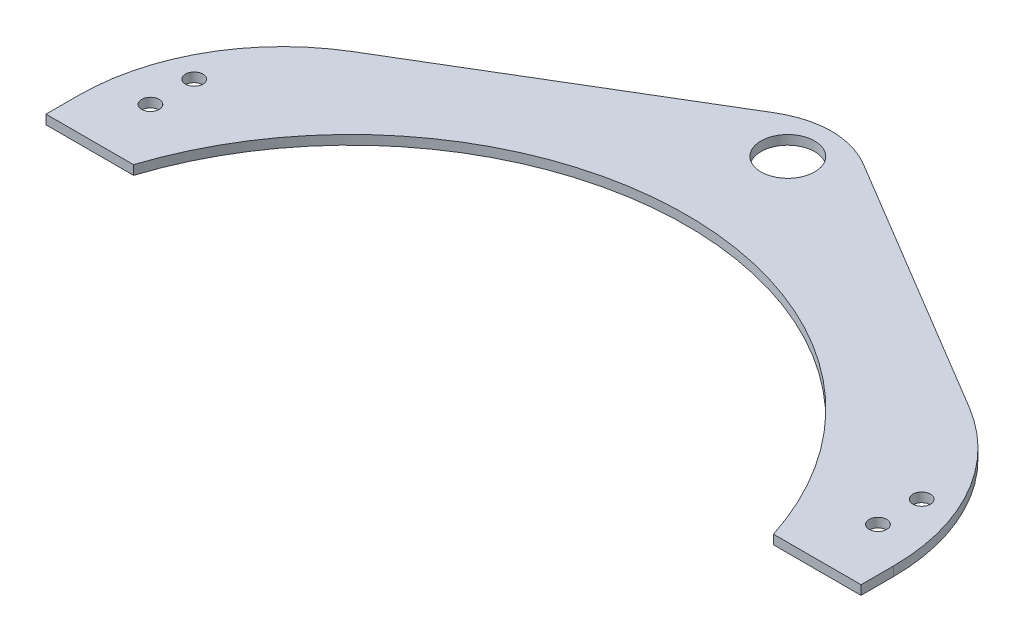
SolidWorks part; units mm, degrees
ref_plane "Front Plane" through (0, 0, 0) normal (0, 0, 1) x (1, 0, 0)
ref_plane "Top Plane" through (0, 0, 0) normal (0, 1, 0) x (1, 0, 0)
ref_plane "Right Plane" through (0, 0, 0) normal (1, 0, 0) x (0, 0, -1)
sketch "Sketch1" plane through (0, 0, 0) normal (0, 1, 0) x (1, 0, 0)
  line L1 (54.85, 0) -> (54.85, 39.9)
  line L2 (109.7, 0) -> (124.7, 0)
  line L3 (0, 0) -> (-15, 0)
  line L4 (124.7, 0) -> (124.7, 16.895)
  line L5 (-15, 0) -> (-15, 16.895)
  line L6 (54.85, 0) -> (54.85, 57.3)
  line L7 (54.85, 57.3) -> (54.85, 64.8)
  line L8 (54.85, 64.8) -> (54.7052, 64.8)
  line L9 (54.85, 64.8) -> (54.9948, 64.8)
  line L10 (62.4068, 62.6719) -> (117.4016, 29.7668)
  line L11 (47.2932, 62.6719) -> (-7.7016, 29.7668)
  line L12 (117.2, 0) -> (117.2, 10.4)
  line L13 (117.2, 10.4) -> (117.2, 17.9)
  line L14 (-7.5, 0) -> (-7.5, 10.4)
  line L15 (107.6704, 35.5893) -> (62.4068, 62.6719)
  line L16 (124.7, 5.5549) -> (124.7, 0)
  line L17 (47.2932, 62.6719) -> (2.0296, 35.5893)
  line L18 (-15, 5.5549) -> (-15, 0)
  line L19 (-7.5, 10.4) -> (-7.5, 17.9)
  circle A1 centre (54.85, 57.3) radius 4.6
  arc A2 (54.7052, 64.8) -> (62.4068, 62.6719) centre (54.7052, 49.8) cw
  arc A3 (54.9948, 64.8) -> (47.2932, 62.6719) centre (54.9948, 49.8) ccw
  arc A4 (-15, 16.895) -> (-7.7016, 29.7668) centre (0, 16.895) cw
  arc A5 (124.7, 16.895) -> (117.4016, 29.7668) centre (109.7, 16.895) ccw
  circle A6 centre (117.2, 17.9) radius 1.5
  circle A7 centre (117.2, 10.4) radius 1.5
  arc A10 (107.6704, 35.5893) -> (124.7, 5.5549) centre (89.7, 5.5549) cw
  arc A11 (2.0296, 35.5893) -> (-15, 5.5549) centre (20, 5.5549) ccw
  circle A13 centre (-7.5, 17.9) radius 1.5
  circle A14 centre (-7.5, 10.4) radius 1.5
  arc A15 (0, 0) -> (109.7, 0) centre (54.85, -17.6788) cw
  point P17 (58.85, 64.8)
  point P20 (50.85, 64.8)
  point P23 (-15, 25.4)
  point P26 (124.7, 25.4)
  point P41 (124.7, 25.4)
  point P44 (-15, 25.4)
  dimension "D8" = 7.5
  dimension "D11" = 15
  dimension "D12" = 15
  dimension "D15" = 10.4
  dimension "D16" = 35
  dimension "D17" = 7.5
  dimension "D1" = 109.7
  dimension "D2" = 39.9
  dimension "D3" = 15
  dimension "D4" = 15
  dimension "D5" = 25.4
  dimension "D6" = 25.4
  dimension "D7" = 57.3
  dimension "D9" = 4
  dimension "D10" = 4
  dimension "D13" = 10.4
  dimension "D14" = 7.5
extrude "Boss-Extrude2" add sketch "Sketch1" along normal blind 1.5875 contours L11 A11 L5 L3 A13 L6 A1 L7 L9 A3 | A10 L10 A2 L8 L7 A1 L6 L2 A7 A6 L4 region at (91.5461, 0, -32.6403) region at (18.1539, 0, -32.6403)
